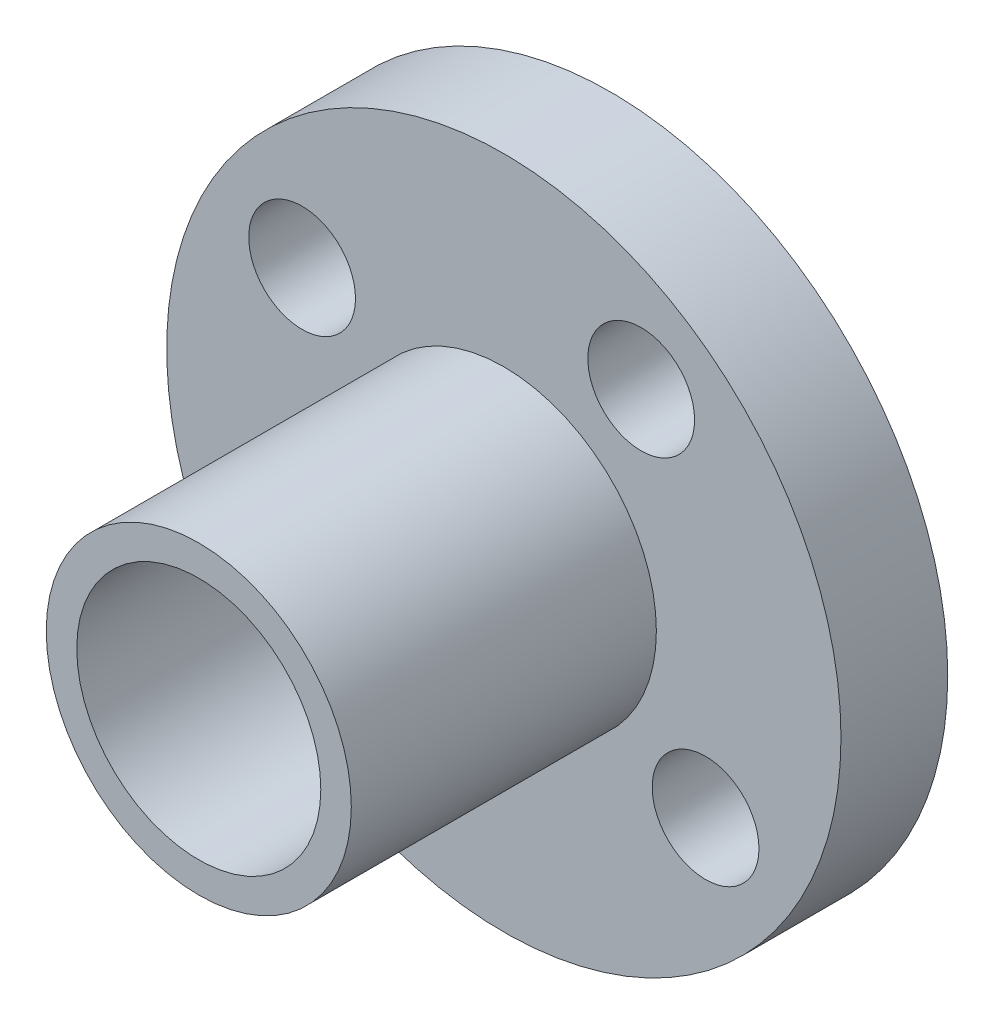
SolidWorks part; units mm, degrees
ref_plane "前视基准面" through (0, 0, 0) normal (0, 0, 1) x (1, 0, 0)
ref_plane "上视基准面" through (0, 0, 0) normal (0, 1, 0) x (1, 0, 0)
ref_plane "右视基准面" through (0, 0, 0) normal (1, 0, 0) x (0, 0, -1)
sketch "草图1" plane through (0, 0, 0) normal (0, 0, 1) x (1, 0, 0)
  circle A0 centre (0, 0) radius 11.0515
  circle A1 centre (0, 0) radius 4
  circle A2 centre (-4.502, -6.613) radius 1.75
  circle A3 centre (-6.613, 4.502) radius 1.75
  circle A4 centre (4.502, 6.613) radius 1.75
  circle A5 centre (6.613, -4.502) radius 1.75
  circle A6 centre (0, 0) radius 5
  point P4 (-4.502, -6.613)
  point P16 (0, 0)
  dimension "D1" = 8
  dimension "D2" = 4
extrude "凸台-拉伸2" add sketch "草图1" along normal blind 3.5 contours A0 A6 A5 A4 A3 A2 region at (-10.7389, 0, 0)
extrude "凸台-拉伸3" add sketch "草图1<5>" along normal blind 13.5 and the other way blind 1.5 contours A6 A1 region at (-4.8586, 0, 0)
sketch "草图1<5>" plane through (0, 0, 0) normal (0, 0, 1) x (1, 0, 0) same geometry as "草图1"
